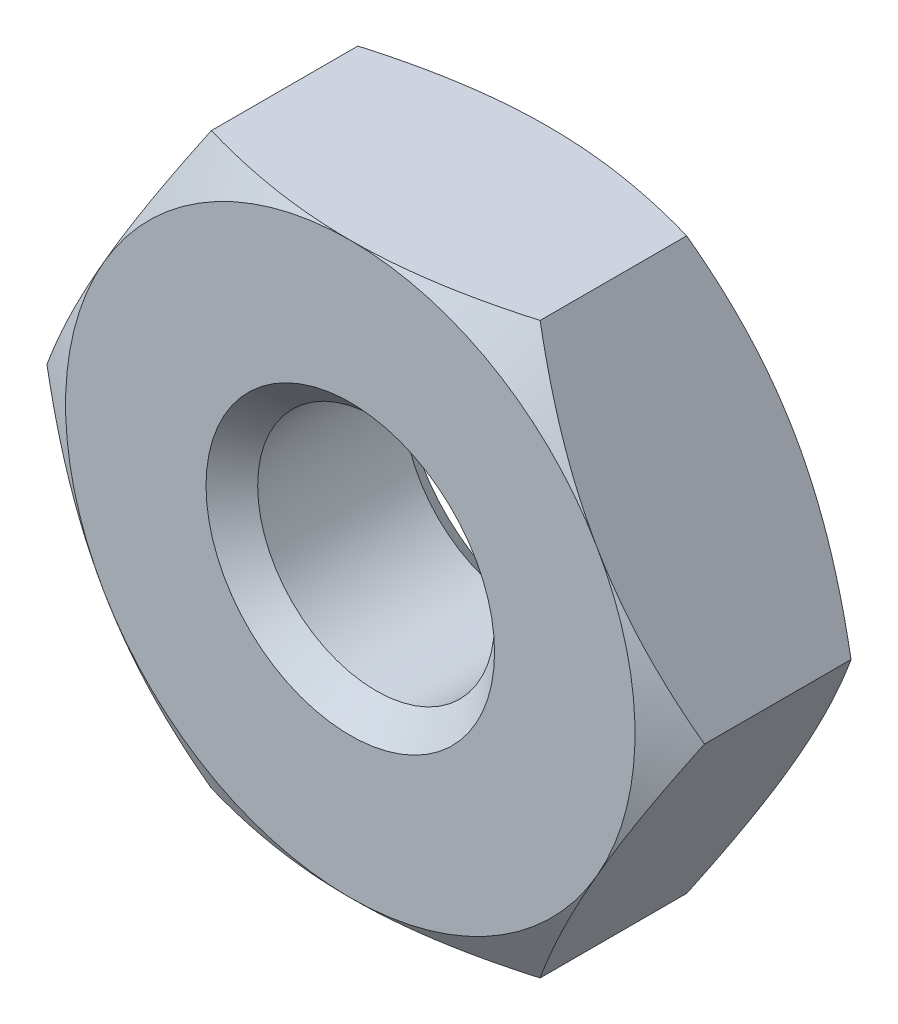
SolidWorks part; units mm, degrees
ref_plane "Front Plane" through (0, 0, 0) normal (0, 0, 1) x (1, 0, 0)
ref_plane "Top Plane" through (0, 0, 0) normal (0, 1, 0) x (1, 0, 0)
ref_plane "Right Plane" through (0, 0, 0) normal (1, 0, 0) x (0, 0, -1)
sketch "Sketch1" plane through (0, 1.651, 0) normal (0, 0, -1) x (-1, 0, 0)
  line L1 (2.7496, 3.1115) -> (-2.7496, 3.1115)
  line L2 (-2.7496, 3.1115) -> (-5.4993, -1.651)
  line L3 (-5.4993, -1.651) -> (-2.7496, -6.4135)
  line L4 (-2.7496, -6.4135) -> (2.7496, -6.4135)
  line L5 (2.7496, -6.4135) -> (5.4993, -1.651)
  line L6 (5.4993, -1.651) -> (2.7496, 3.1115)
  circle A0 centre (0, -1.651) radius 4.7625 construction
  dimension "D1" = 9.525
extrude "Boss-Extrude1" add sketch "Sketch1" against normal mid plane 3.302
sketch "Sketch2" plane through (0, 0, 0) normal (0, 1, 0) x (-1, 0, 0)
  line L0 (-5.4993, -1.2256) -> (-5.4993, -1.651)
  line L1 (-5.4993, -1.651) -> (-4.7625, -1.651)
  line L2 (-4.7625, -1.651) -> (-5.4993, -1.2256)
  line L3 (0, 0) -> (0, -1.651) construction
  line L4 (-5.4993, 1.651) -> (-5.4993, -1.651) construction
  line L5 (-2.7496, -1.651) -> (-5.4993, -1.651) construction
  point P5 (0.0151, -0.9698)
  point P8 (-4.7625, -1.1759)
  point P11 (0, 0)
  dimension "D1" = 0.7368
  dimension "D2" = 5.4993
  dimension "D3" = 0.4254
revolve "Cut-Revolve1" cut sketch "Sketch2" angle 360 about L3 reverse direction yes
sketch "Sketch4" plane through (0, 0, 0) normal (0, 1, 0) x (1, 0, 0)
  line L0 (2.413, 1.651) -> (0, 1.651)
  line L1 (0, 1.651) -> (0, -1.2192)
  line L2 (0, -1.2192) -> (1.9812, -1.2192)
  line L3 (1.9812, -1.2192) -> (1.9812, 1.2192)
  line L4 (1.9812, 1.2192) -> (2.413, 1.651)
  line L5 (0, 1.651) -> (0, -1.2192) construction
  line L6 (4.1244, 1.651) -> (0, 1.651) construction
  point P5 (0.4313, -1.1874)
  point P6 (0, -1.2715)
  dimension "D1" = 1.9812
  dimension "D2" = 2.413
  dimension "D3" = 0.4318
  dimension "D4" = 2.8702
revolve "Cut-Revolve3" cut sketch "Sketch4" angle 360 about L5 reverse direction yes
mirror "Mirror1" about plane through (0, 0, 0) normal (0, 0, 1) of "Cut-Revolve1", "Cut-Revolve3"
